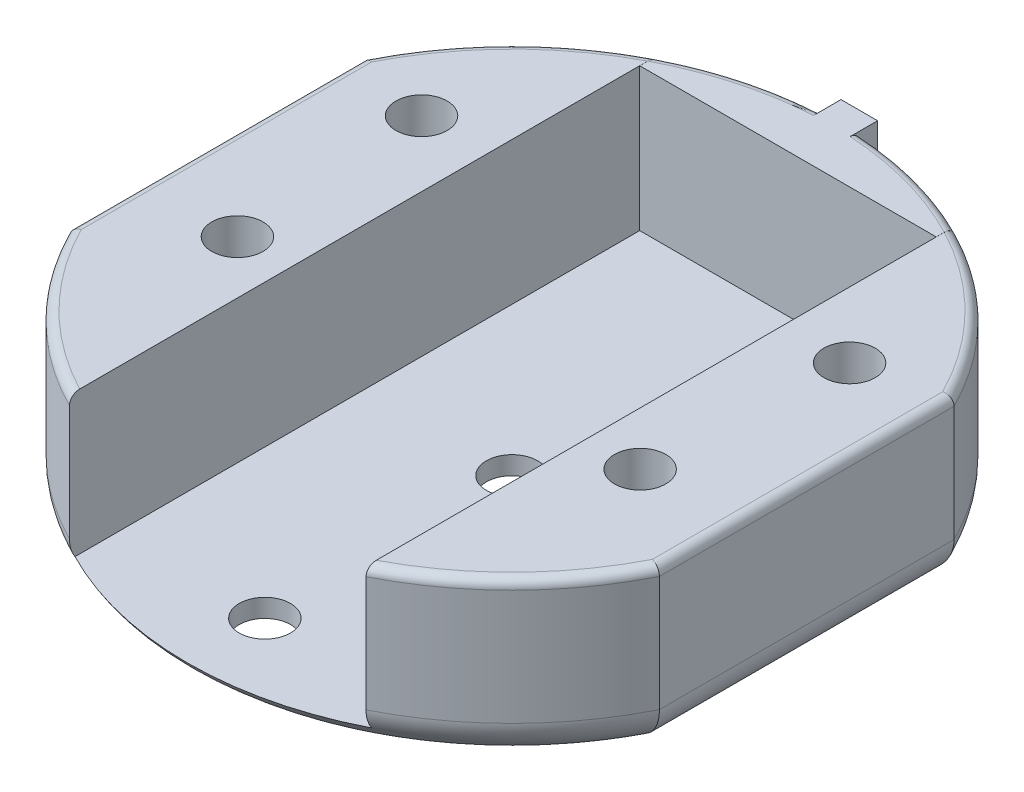
SolidWorks part; units mm, degrees
ref_plane "Front Plane" through (0, 0, 0) normal (0, 0, 1) x (1, 0, 0)
ref_plane "Top Plane" through (0, 0, 0) normal (0, 1, 0) x (1, 0, 0)
ref_plane "Right Plane" through (0, 0, 0) normal (1, 0, 0) x (0, 0, -1)
sketch "Sketch1" plane through (0, 0, 0) normal (0, 1, 0) x (1, 0, 0)
  line L0 (-1, 17.9722) -> (-1, 18.9722)
  line L1 (-1, 18.9722) -> (1, 18.9722)
  line L2 (1, 18.9722) -> (1, 17.9722)
  line L3 (0, 18.9722) -> (0, 0) construction
  arc A0 (-1, 17.9722) -> (1, 17.9722) centre (0, 0) ccw
  dimension "D1" = 36
  dimension "D2" = 2
  dimension "D3" = 1
extrude "Boss-Extrude1" add sketch "Sketch1" along normal blind 1
sketch "Sketch2" plane through (0, 0, 0) normal (0, 0, 1) x (1, 0, 0)
  line L0 (18, 1) -> (-18, 1) construction
  line L1 (0, 9) -> (-10.9803, 9) construction
  line L2 (-16.1, 8.8) -> (-8.1, 8.8)
  line L3 (-16.1, 8.8) -> (-16.1, 1)
  line L4 (8.1, 8.8) -> (16.1, 8.8)
  line L5 (16.1, 8.8) -> (16.1, 1)
  line L6 (0, 9) -> (0, 0) construction
  line L8 (-8.1, 8.8) -> (-8.1, 1)
  line L9 (-8, 1) -> (8, 1) construction
  line L10 (-8, 1) -> (-8, 17) construction
  line L11 (-8, 17) -> (8, 17) construction
  line L12 (8, 1) -> (8, 17) construction
  line L13 (-8, 1) -> (8, 17) construction
  line L14 (-8, 17) -> (8, 1) construction
  line L16 (8.1, 8.8) -> (8.1, 1)
  line L17 (-8.1, 1) -> (-16.1, 1)
  line L18 (16.1, 1) -> (8.1, 1)
  point P14 (16.1, 11.7725)
  dimension "D1" = 16
  dimension "D2" = 0.1
  dimension "D3" = 0.1
  dimension "D4" = 0.2
  dimension "D5" = 8
extrude "Boss-Extrude2" add sketch "Sketch2" along normal through all and the other way through all
sketch "Sketch3" plane through (0, 0, 0) normal (0, -1, 0) x (1, 0, 0)
  line L3 (-1, -17.9722) -> (-1, -18.9722)
  line L4 (-1, -18.9722) -> (1, -18.9722)
  line L5 (1, -18.9722) -> (1, -17.9722)
  line L6 (-1, -17.9722) -> (-1, -18.9722)
  line L7 (-1, -18.9722) -> (1, -18.9722)
  line L8 (1, -18.9722) -> (1, -17.9722)
  circle A0 centre (0, 0) radius 59.9105
  arc A1 (1, -17.9722) -> (-1, -17.9722) centre (0, 0) ccw
  arc A2 (1, -17.9722) -> (-1, -17.9722) centre (0, 0) ccw
  dimension "D1" = 0
extrude "Cut-Extrude1" cut sketch "Sketch3" against normal through all
sketch "Sketch5" plane through (0, 0, 0) normal (0, 1, 0) x (1, 0, 0)
  line L0 (-11, -4) -> (11, -4) construction
  line L1 (0, -4) -> (0, 0) construction
  circle A0 centre (0, 0) radius 1.4
  circle A2 centre (11, -4) radius 1.4
  circle A4 centre (-11, -4) radius 1.4
  arc A6 (0, -14.525) -> (0, -12.475) centre (0, -13.5) ccw construction
  arc A7 (-11.6913, 7.775) -> (-11.6913, 5.725) centre (-11.6913, 6.75) ccw construction
  arc A8 (0, -14.525) -> (0, -12.475) centre (0, -13.5) ccw construction
  arc A9 (11.6913, 5.725) -> (11.6913, 7.775) centre (11.6913, 6.75) ccw construction
  arc A10 (-11.6913, 7.775) -> (-11.6913, 5.725) centre (-11.6913, 6.75) ccw construction
  arc A11 (11.6913, 5.725) -> (11.6913, 7.775) centre (11.6913, 6.75) ccw construction
  circle A13 centre (-11.6913, 6.75) radius 1.4
  circle A15 centre (0, -13.5) radius 1.4
  circle A17 centre (11.6913, 6.75) radius 1.4
  dimension "D1" = 2.8
  dimension "D2" = 2.8
  dimension "D3" = 22
  dimension "D4" = 4
extrude "Cut-Extrude2" cut sketch "Sketch5" against normal through all and the other way through all
sketch "Sketch6" plane through (0, 0, 0) normal (0, -1, 0) x (1, 0, 0)
  line L0 (-8.0975, -15.0758) -> (8.0975, -15.0758)
  line L4 (-8.0975, -15.0758) -> (-8.0975, -16.0758)
  line L5 (8.0975, -15.0758) -> (8.0975, -16.0758)
  line L17 (1, -18.9722) -> (1, -17.9722)
  line L18 (-1, -18.9722) -> (1, -18.9722)
  line L19 (-1, -17.9722) -> (-1, -18.9722)
  arc A7 (1, -17.9722) -> (8.0975, -16.0758) centre (0, 0) ccw
  arc A8 (-8.0975, -16.0758) -> (-1, -17.9722) centre (0, 0) ccw
  point P2 (0, 0)
  point P4 (0, 0)
  point P5 (0, 0)
  point P8 (0, 0)
  dimension "D1" = 1
extrude "Boss-Extrude3" add sketch "Sketch6" against normal up to surface (8.8 mm away) up to face at (-13.0913, 8.8, -6.75)
sketch "Sketch7" plane through (0, 1, 0) normal (0, 1, 0) x (1, 0, 0)
  line L0 (16.1, 8.0492) -> (16.1, -8.0492) construction
  line L1 (-16.1, -8.0492) -> (-16.1, 8.0492) construction
  line L2 (16.1, 8.0492) -> (16.1, -8.0492)
  line L3 (-16.1, -8.0492) -> (-16.1, 8.0492)
  arc A0 (16.1, -8.0492) -> (16.1, 8.0492) centre (0, 0) ccw construction
  arc A1 (-16.1, 8.0492) -> (-16.1, -8.0492) centre (0, 0) ccw construction
  arc A2 (16.1, -8.0492) -> (16.1, 8.0492) centre (0, 0) ccw
  arc A3 (-16.1, 8.0492) -> (-16.1, -8.0492) centre (0, 0) ccw
extrude "Cut-Extrude3" cut sketch "Sketch7" against normal through all
fillet "Fillet1" radius 2 3 edges at (16.1, 0, 0) (-16.1, 0, 0) (0, 0, 18)
fillet "Fillet2" radius 0.5 8 edges at (4.6465, 8.8, -17.3899) (-4.6465, 8.8, -17.3899) (16.1, 8.8, 0) (-16.1, 8.8, 0) (-12.748, 8.8, 12.7078) (-12.748, 8.8, -12.7078) (12.748, 8.8, 12.7078) (12.748, 8.8, -12.7078)
